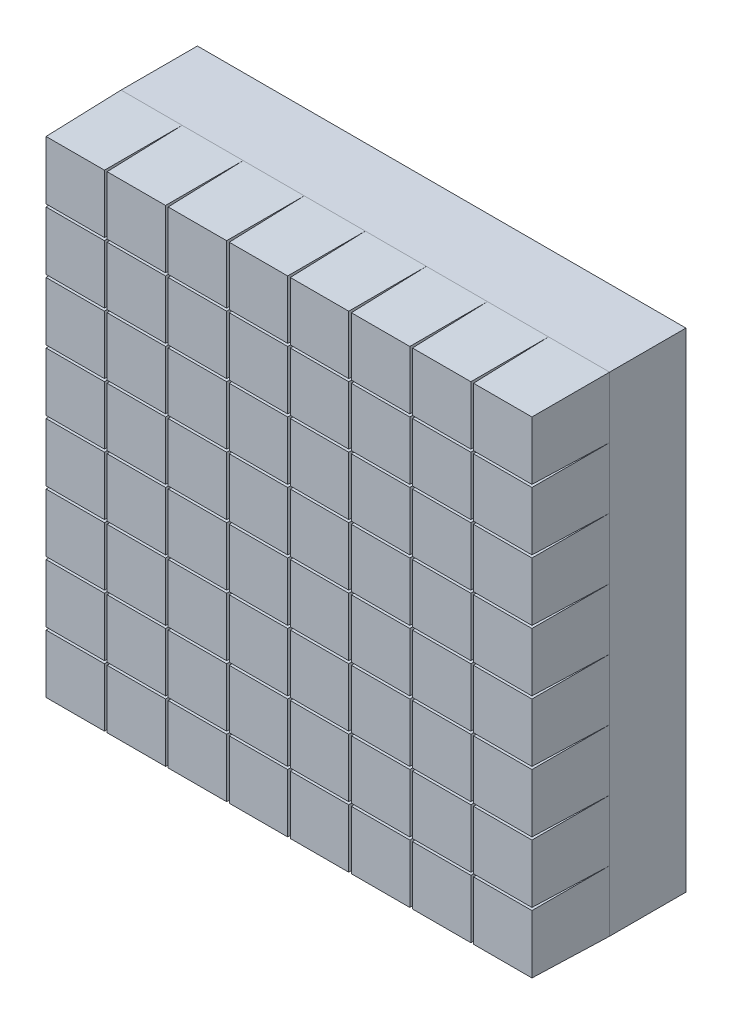
SolidWorks part; units mm, degrees
ref_plane "Спереди" through (0, 0, 0) normal (0, 0, 1) x (1, 0, 0)
ref_plane "Сверху" through (0, 0, 0) normal (0, 1, 0) x (1, 0, 0)
ref_plane "Справа" through (0, 0, 0) normal (1, 0, 0) x (0, 0, -1)
sketch "Эскиз2" plane through (0, 0, 0) normal (0, 0, 1) x (1, 0, 0)
  line L1 (0, 0) -> (64, 0)
  line L2 (0, 0) -> (0, 64)
  line L3 (0, 64) -> (64, 64)
  line L4 (64, 0) -> (64, 64)
  dimension "D1" = 64
  dimension "D2" = 64
extrude "Бобышка-Вытянуть2" add sketch "Эскиз2" along normal blind 10
sketch "Эскиз4" plane through (0, 0, 10) normal (0, 0, 1) x (1, 0, 0)
  line L0 (0, 64) -> (0, 0)
  line L1 (0, 64) -> (0, 0)
  line L2 (8, 64) -> (8, 0)
  line L3 (16, 64) -> (16, 0)
  line L4 (24, 64) -> (24, 0)
  line L5 (32, 64) -> (32, 0)
  line L6 (40, 64) -> (40, 0)
  line L7 (48, 64) -> (48, 0)
  line L8 (56, 64) -> (56, 0)
  line L9 (64, 64) -> (64, 0)
  line L10 (0, 64) -> (64, 64)
  line L11 (0, 0) -> (64, 0)
  line L12 (0, 0) -> (64, 0)
  line L13 (0, 8) -> (64, 8)
  line L14 (0, 16) -> (64, 16)
  line L15 (0, 24) -> (64, 24)
  line L16 (0, 32) -> (64, 32)
  line L17 (0, 40) -> (64, 40)
  line L18 (0, 48) -> (64, 48)
  line L19 (0, 56) -> (64, 56)
  line L20 (0, 64) -> (64, 64)
  line M1 (0, 64) -> (0, 0)
  line M2 (0, 0) -> (64, 0)
  line M3 (64, 0) -> (64, 64)
  line M4 (64, 64) -> (0, 64)
  dimension "D1" = 9
  dimension "D2" = 9
extrude "Бобышка-Вытянуть10" add sketch "Эскиз4" along normal blind 10 draft 1 separate body contours L19 L2 M1 M4 | L19 L2 L18 L3 | L3 L19 L4 M4 | L19 L4 L18 L5 | L5 L19 L6 M4 | L19 L6 L18 L7 | L7 L19 L8 M4 | L19 L8 L18 M3 | L18 L7 L17 L8 | L17 L6 L16 L7 | L18 L5 L17 L6 | L17 L4 L16 L5 | L18 L3 L17 L4 | L17 L2 L16 L3 | L18 L1 L17 L2 | L16 L1 L15 L2 | L15 L2 L14 L3 | L16 L3 L15 L4 | L15 L4 L14 L5 | L16 L5 L15 L6 | L15 L6 L14 L7 | L16 L7 L15 L8 | L17 L8 L16 M3 | L15 L8 L14 M3 | L14 L7 L13 L8 | L13 L8 M2 M3 | L13 L6 L7 M2 | L14 L5 L13 L6 | L13 L4 L5 M2 | L14 L3 L13 L4 | L13 L2 L3 M2 | L14 L1 L13 L2 region at (4, 60, 10) region at (4, 44, 10) region at (12, 52, 10) region at (20, 60, 10) region at (4, 28, 10) region at (12, 36, 10) region at (20, 44, 10) region at (28, 52, 10) region at (36, 60, 10) region at (4, 12, 10) region at (12, 20, 10) region at (20, 28, 10) region at (28, 36, 10) region at (36, 44, 10) region at (44, 52, 10) region at (52, 60, 10) region at (12, 4, 10) region at (20, 12, 10) region at (28, 20, 10) region at (36, 28, 10) region at (44, 36, 10) region at (52, 44, 10) region at (60, 52, 10) region at (28, 4, 10) region at (36, 12, 10) region at (44, 20, 10) region at (52, 28, 10) region at (60, 36, 10) region at (44, 4, 10) region at (52, 12, 10) region at (60, 20, 10) region at (60, 4, 10)
extrude "Бобышка-Вытянуть11" add sketch "Эскиз4<5>" along normal blind 10 draft 1 separate body contours L13 L1 L2 M2 | L14 L2 L13 L3 | L13 L3 L4 M2 | L14 L4 L13 L5 | L13 L5 L6 M2 | L14 L6 L13 L7 | L13 L7 L8 M2 | L14 L8 L13 L9 | L15 L7 L14 L8 | L15 L5 L14 L6 | L16 L4 L15 L5 | L15 L3 L14 L4 | L15 L1 L14 L2 | L16 L2 L15 L3 | L17 L1 L16 L2 | L17 L3 L16 L4 | L17 L5 L16 L6 | L16 L6 L15 L7 | L17 L7 L16 L8 | L16 L8 L15 L9 | L18 L8 L17 L9 | L19 L7 L18 L8 | L8 L19 L9 M4 | L6 L19 L7 M4 | L19 L5 L18 L6 | L18 L6 L17 L7 | L18 L4 L17 L5 | L19 L3 L18 L4 | L4 L19 L5 M4 | L2 L19 L3 M4 | L19 L1 L18 L2 | L18 L2 L17 L3 region at (4, 52, 10) region at (12, 60, 10) region at (4, 36, 10) region at (12, 44, 10) region at (20, 52, 10) region at (28, 60, 10) region at (4, 20, 10) region at (12, 28, 10) region at (20, 36, 10) region at (28, 44, 10) region at (36, 52, 10) region at (44, 60, 10) region at (4, 4, 10) region at (12, 12, 10) region at (20, 20, 10) region at (28, 28, 10) region at (36, 36, 10) region at (44, 44, 10) region at (52, 52, 10) region at (60, 60, 10) region at (20, 4, 10) region at (28, 12, 10) region at (36, 20, 10) region at (44, 28, 10) region at (52, 36, 10) region at (60, 44, 10) region at (36, 4, 10) region at (44, 12, 10) region at (52, 20, 10) region at (60, 28, 10) region at (52, 4, 10) region at (60, 12, 10)
sketch "Эскиз4<5>" plane through (0, 0, 10) normal (0, 0, 1) x (1, 0, 0) same geometry as "Эскиз4"
